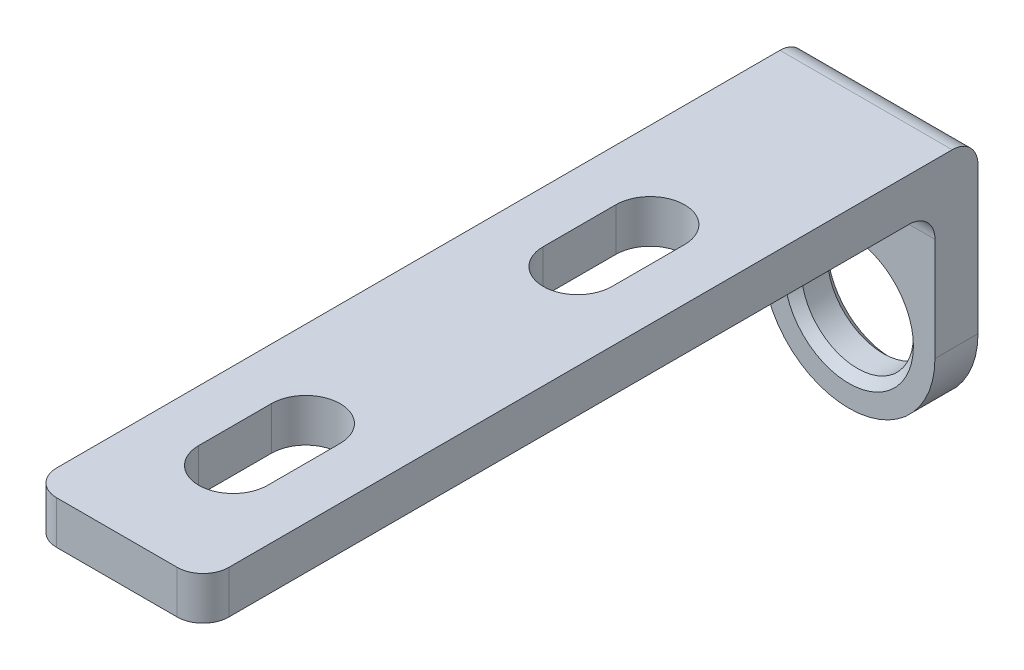
SolidWorks part; units mm, degrees
ref_plane "Front Plane" through (0, 0, 0) normal (0, 0, 1) x (1, 0, 0)
ref_plane "Top Plane" through (0, 0, 0) normal (0, 1, 0) x (1, 0, 0)
ref_plane "Right Plane" through (0, 0, 0) normal (1, 0, 0) x (0, 0, -1)
sketch "Sketch1" plane through (0, 0, 0) normal (1, 0, 0) x (0, 0, -1)
  line L0 (-49.7872, 21.7693) -> (40.2128, 21.7693)
  line L1 (40.2128, 21.7693) -> (40.2128, -8.2307)
  line L2 (40.2128, -8.2307) -> (35.2128, -8.2307)
  line L3 (35.2128, -8.2307) -> (35.2128, 16.7693)
  line L4 (35.2128, 16.7693) -> (-49.7872, 16.7693)
  line L5 (-49.7872, 16.7693) -> (-49.7872, 21.7693)
  dimension "D1" = 90
  dimension "D2" = 5
  dimension "D3" = 5
  dimension "D4" = 30
extrude "Boss-Extrude1" add sketch "Sketch1" along normal blind 20
sketch "Sketch2" plane through (0, 16.7693, 0) normal (0, -1, 0) x (1, 0, 0)
  line L0 (10, 36.2836) -> (10, 27.8557) construction
  line L1 (14, 36.2836) -> (14, 27.8557)
  line L2 (6, 36.2836) -> (6, 27.8557)
  line L3 (20, 49.7872) -> (20, -35.2128) construction
  arc A1 (14, 36.2836) -> (6, 36.2836) centre (10, 36.2836) ccw
  arc A2 (6, 27.8557) -> (14, 27.8557) centre (10, 27.8557) ccw
  point P2 (10, 32.0696)
  dimension "D1" = 4
  dimension "D2" = 10
extrude "Cut-Extrude1" cut sketch "Sketch2" against normal blind 20
pattern_linear "LPattern1" count 2 spacing 40 along (0, 0, -1) of "Cut-Extrude1"
sketch "Sketch3" plane through (0, 0, -35.2128) normal (0, 0, 1) x (1, 0, 0)
  line L0 (20, -8.2307) -> (0, -8.2307) construction
  line L1 (20, 16.7693) -> (20, -8.2307) construction
  circle A0 centre (10, 1.7693) radius 6.5
  dimension "D1" = 10
  dimension "D3" = 13
  dimension "D2" = 10
extrude "Cut-Extrude2" cut sketch "Sketch3" against normal blind 20
fillet "Fillet1" radius 3 2 edges at (10, 16.7693, -35.2128) (10, 21.7693, -40.2128)
fillet "Fillet2" radius 10 2 edges at (0, -8.2307, -37.7128) (20, -8.2307, -37.7128)
chamfer "Chamfer1" distance 1 angle 45 2 edges at (10, -4.7307, -40.2128) (16.5, 1.7693, -35.2128)
fillet "Fillet3" radius 3 2 edges at (20, 19.2693, 49.7872) (0, 19.2693, 49.7872)
